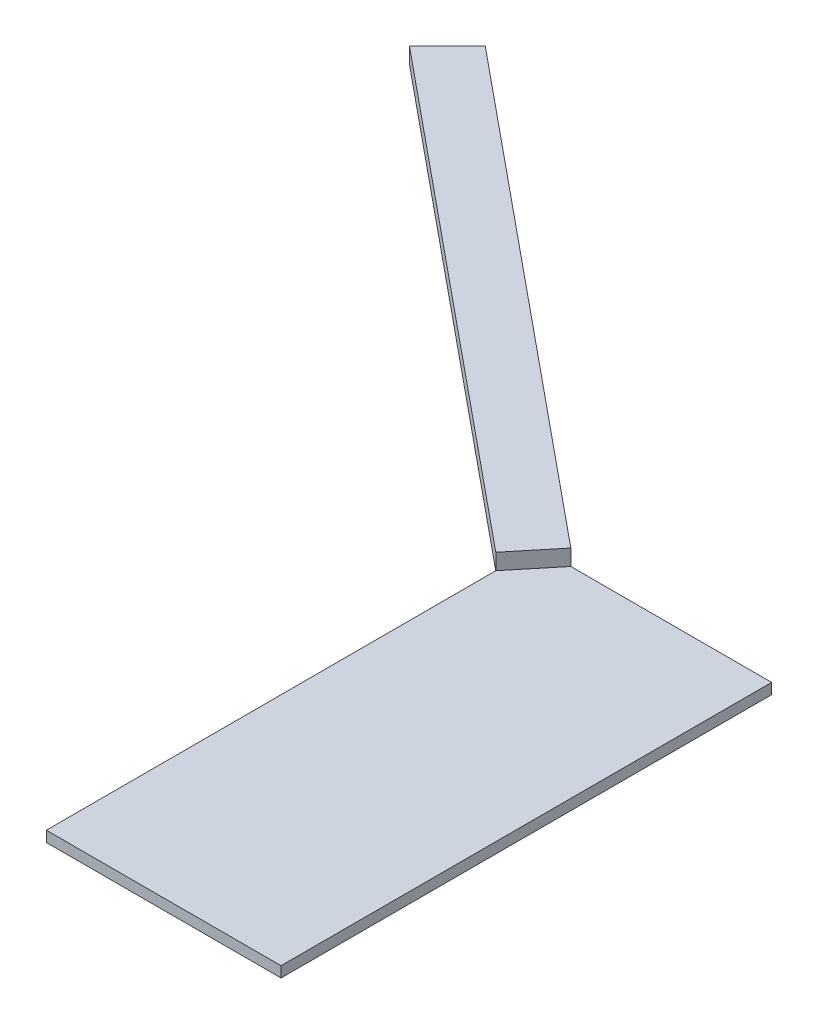
SolidWorks part; units mm, degrees
ref_plane "Front Plane" through (0, 0, 0) normal (0, 0, 1) x (1, 0, 0)
ref_plane "Top Plane" through (0, 0, 0) normal (0, 1, 0) x (1, 0, 0)
ref_plane "Right Plane" through (0, 0, 0) normal (1, 0, 0) x (0, 0, -1)
sketch "Sketch1" plane through (0, 0, 0) normal (0, 1, 0) x (1, 0, 0)
  line L0 (-139.7, -292.1) -> (139.7, 292.1) construction
  line L1 (-139.7, 292.1) -> (139.7, 292.1)
  line L2 (-139.7, 292.1) -> (-139.7, -292.1)
  line L3 (-139.7, -292.1) -> (139.7, -292.1)
  line L4 (139.7, 292.1) -> (139.7, -292.1)
  line L5 (0, 0) -> (0, 232.3863) construction
  line L6 (0, 0) -> (300.98, 0) construction
  line L7 (-984.25, 381) -> (984.25, 381) construction
  line L8 (-381, 292.1) -> (381, 292.1)
  line L9 (-381, 292.1) -> (-381, -469.9)
  line L10 (-381, -469.9) -> (381, -469.9)
  line L11 (381, 292.1) -> (381, -469.9)
  line L12 (-984.25, 381) -> (0, 1365.25) construction
  line L13 (0, 1365.25) -> (984.25, 381) construction
  line L14 (-730.25, 635) -> (730.25, 635) construction
  circle A0 centre (0, 1365.25) radius 304.8 construction
  circle A1 centre (-427.1108, 635) radius 44.45
  circle A2 centre (427.1108, 635) radius 44.45
  point P4 (0, 0)
  dimension "D7" = 609.6
  dimension "D9" = 88.9
  dimension "D1" = 584.2
  dimension "D2" = 279.4
  dimension "D3" = 762
  dimension "D4" = 88.9
  dimension "D5" = 1968.5
  dimension "D6" = 984.25
  dimension "D8" = 254
extrude "Boss-Extrude1" add sketch "Sketch1" along normal blind 12.7 contours L1 L2 L3 | L1 L3 L4 region at (0, 0, 0)
sketch "Sketch2" plane through (0, 0, 0) normal (0, 1, 0) x (1, 0, 0)
  line L0 (-984.25, 381) -> (0, 1365.25) construction
  line L1 (-988.2038, 438.6215) -> (-373.9346, 1052.8907)
  line L2 (-804.2183, 622.6069) -> (-381, 292.1)
  circle A0 centre (-840.7448, 524.5052) radius 38.1
  circle A1 centre (-624.2672, 740.9828) radius 38.1
  circle A2 centre (-398.6168, 966.6332) radius 38.1
sketch "Sketch3" plane through (0, 12.7, 0) normal (0, 1, 0) x (1, 0, 0)
  line L0 (-139.7, 243.0161) -> (-99.4133, 292.1)
  line L1 (-99.4133, 292.1) -> (-668.0249, 758.8004)
  line L2 (-478.8545, 619.9647) -> (-382.49, 540.8714) construction
  line L3 (-988.2038, 438.6215) -> (-373.9346, 1052.8907) construction
  line L4 (139.7, -292.1) -> (139.7, 292.1)
  line L5 (139.7, 292.1) -> (-139.7, 292.1)
  line L6 (-139.7, 292.1) -> (-139.7, -292.1)
  line L7 (-139.7, -292.1) -> (139.7, -292.1)
  line L8 (139.7, -292.1) -> (139.7, 292.1)
  line L9 (139.7, 292.1) -> (-139.7, 292.1)
  line L10 (-139.7, 292.1) -> (-139.7, -292.1)
  line L11 (-139.7, -292.1) -> (139.7, -292.1)
  line L12 (-139.7, 243.0161) -> (-713.1432, 713.6821)
  line L13 (-713.1432, 713.6821) -> (-668.0249, 758.8004)
  circle A0 centre (-427.1108, 635) radius 44.45 construction
  circle A1 centre (-427.1108, 635) radius 44.45
  dimension "D2" = 63.5
  dimension "D3" = 25.4
  dimension "D1" = 0
extrude "Boss-Extrude2" add sketch "Sketch3" along normal blind 19.05 separate body contours L13 L12 L10 L9 L1 | L9 L10 L0 region at (-126.2711, 12.7, -275.7387) region at (-411.1038, 12.7, -506.7351)
